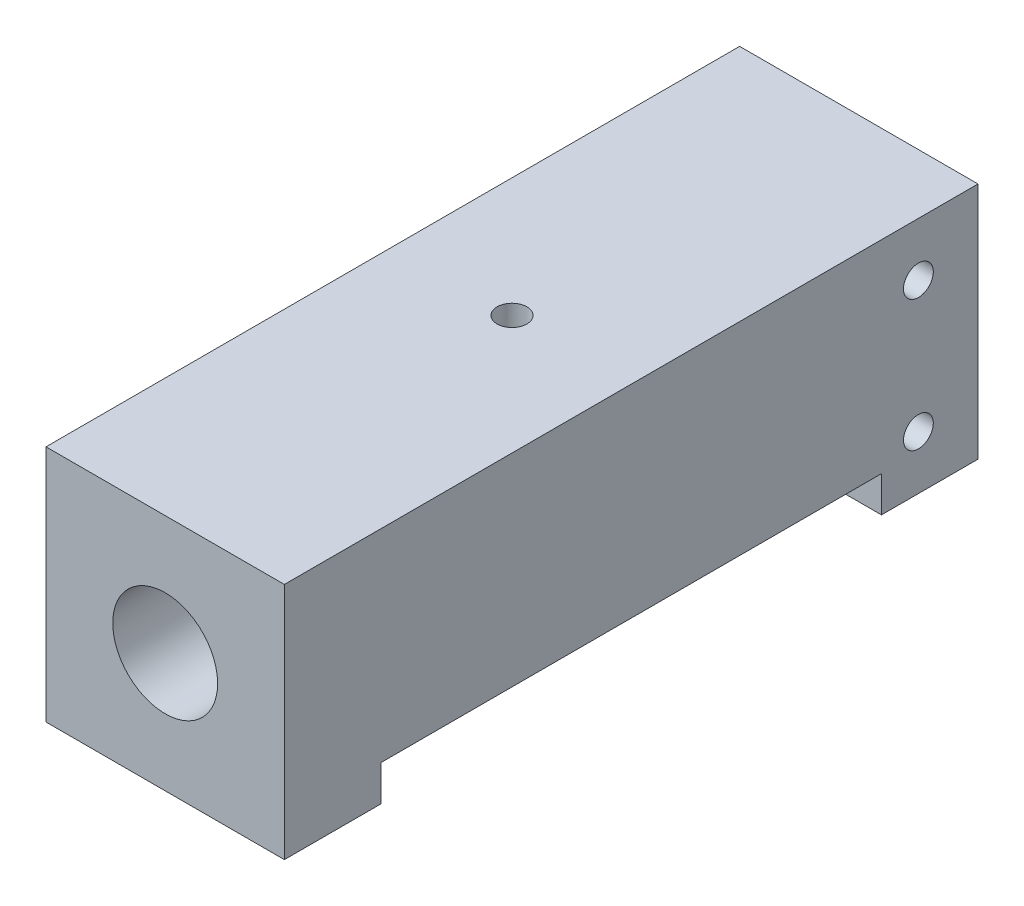
SolidWorks part; units mm, degrees
material "6063-T5"
ref_plane "Piano frontale" through (0, 0, 0) normal (0, 0, 1) x (1, 0, 0)
ref_plane "Piano superiore" through (0, 0, 0) normal (0, 1, 0) x (1, 0, 0)
ref_plane "Piano destro" through (0, 0, 0) normal (1, 0, 0) x (0, 0, -1)
sketch "Schizzo1" plane through (0, 0, 0) normal (0, 0, 1) x (1, 0, 0)
  line L1 (10, -10) -> (-10, -10)
  line L2 (10, -10) -> (10, 10)
  line L3 (10, 10) -> (-10, 10)
  line L4 (-10, -10) -> (-10, 10)
  line L5 (10, -10) -> (-10, 10) construction
  line L6 (10, 10) -> (-10, -10) construction
  point P0 (0, 0)
  dimension "D1" = 20
  dimension "D2" = 20
extrude "Estrusione-Estrusione1" add sketch "Schizzo1" against normal blind 58.2
sketch "Schizzo2" plane through (0, 0, -58.2) normal (0, 0, -1) x (-1, 0, 0)
  circle A0 centre (0, 0) radius 3
  dimension "D1" = 6
extrude "Taglio-Estrusione1" cut sketch "Schizzo2" against normal through all
sketch "Schizzo3" plane through (0, 0, -58.2) normal (0, 0, -1) x (-1, 0, 0)
  point P0 (0, 0)
hole_wizard "Foro filettato G1/8-1" positions "Schizzo8" profile "Schizzo7" tap size "G1/8" standard "BSI"
sketch "Schizzo8" plane through (0, 0, 0) normal (0, 0, 1) x (1, 0, 0)
  point P0 (0, 0)
sketch "Schizzo7" plane through (0, 0, 0) normal (1, 0, 0) x (0, -1, 0)
  line L0 (0, 0) -> (0, 12.6438)
  line L1 (0, 12.6438) -> (4.4, 10)
  line L2 (4.4, 10) -> (4.4, 0)
  line L5 (4.4, 0) -> (0, 0)
  line L10 (0, 12.6438) -> (-4.4, 10) construction
  line L11 (0, -6.35) -> (0, 107.95) construction
  dimension "Tap Drill Dia." = 8.8
  dimension "Tap Drill Depth" = 10
  dimension "Drill Angle" = 118
sketch "Schizzo11" plane through (0, 10, 0) normal (0, 1, 0) x (1, 0, 0)
  line L0 (0, 58.2) -> (0, 0) construction
  line L1 (10, 58.2) -> (-10, 58.2) construction
  line L2 (10, 29.1) -> (-10, 29.1) construction
  line L3 (10, 58.2) -> (10, 0) construction
  point P10 (0, 29.1)
  point P11 (0, 29.1)
  point P12 (0, 29.1)
hole_wizard "M3 Tapped Hole2" positions "Schizzo3D1" profile "Schizzo12" tap size "M3" standard "DIN"
sketch3d "Schizzo3D1"
  point P0 (0, 10, -29.1)
sketch "Schizzo12" plane through (0, 10, -29.1) normal (1, 0, 0) x (0, 0, 1)
  line L0 (0, 0) -> (0, 5.7511)
  line L1 (0, 5.7511) -> (1.25, 5)
  line L2 (1.25, 5) -> (1.25, 0)
  line L5 (1.25, 0) -> (0, 0)
  line L10 (0, 5.7511) -> (-1.25, 5) construction
  line L11 (0, -6.35) -> (0, 107.95) construction
  dimension "Tap Drill Dia." = 2.5
  dimension "Tap Drill Depth" = 5
  dimension "Drill Angle" = 118
cosmetic thread "Hole Thread4" parameters "D1"=5, "D2"=3
hole_wizard "Foro Ø16.0 (16)-1" positions "Schizzo3D3" profile "Schizzo14" hole size "Ø16.0" standard "ISO"
sketch3d "Schizzo3D3"
  point P0 (0, 0, 0)
  point P3 (0, 0, -58.2)
sketch "Schizzo14" plane through (0, 0, -58.2) normal (1, 0, 0) x (0, 1, 0)
  line L0 (0, 0) -> (0, 16.8069)
  line L1 (0, 16.8069) -> (8, 12)
  line L2 (8, 12) -> (8, 0)
  line L5 (8, 0) -> (0, 0)
  line L10 (0, 16.8069) -> (-8, 12) construction
  line L11 (0, -6.35) -> (0, 107.95) construction
  dimension "Hole Dia." = 16
  dimension "Hole Depth" = 12
  dimension "Drill Angle" = 118
sketch "Schizzo15" plane through (10, 0, 0) normal (1, 0, 0) x (0, 0, -1)
  line L0 (46.2, 0) -> (58.2, 0) construction
  line L1 (46.2, 8) -> (46.2, -8) construction
  line L4 (58.2, -10) -> (58.2, 10) construction
  line L6 (58.2, -10) -> (0, -10) construction
  point P5 (53.2, -5.5)
  point P8 (53.2, 5.5)
  dimension "D1" = 5.5
  dimension "D2" = 7
  dimension "D3" = 5
  dimension "D4" = 4.5
hole_wizard "M3 Tapped Hole3" positions "Schizzo3D4" profile "Schizzo16" tap size "M3" standard "ISO" end condition through all
sketch3d "Schizzo3D4"
  point P0 (10, 5.5, -53.2)
  point P3 (10, -5.5, -53.2)
sketch "Schizzo16" plane through (10, 5.5, -53.2) normal (0, 1, 0) x (0, 0, -1)
  line L0 (0, 0) -> (0, 20)
  line L1 (0, 20) -> (1.25, 20)
  line L2 (1.25, 20) -> (1.25, 0)
  line L5 (1.25, 0) -> (0, 0)
  line L11 (0, -6.35) -> (0, 107.95) construction
  dimension "Thread Major Dia." = 2.5
  dimension "Thru Tap Drill Depth" = 20
sketch "Sketch1" plane through (-10, 0, 0) normal (-1, 0, 0) x (0, 0, 1)
  line L0 (-58.2, 10) -> (-58.2, -10) construction
  line L1 (-58.2, 3) -> (-22, 3)
  line L2 (-58.2, 3) -> (-58.2, -3)
  line L3 (-58.2, -3) -> (-22, -3)
  line L4 (-22, 3) -> (-22, -3)
  line L5 (0, 10) -> (0, -10) construction
  line L6 (0, 0) -> (-22, 0) construction
  point P8 (-22, 0)
  dimension "D1" = 6
  dimension "D2" = 22
extrude "Boss-Extrude1" add sketch "Sketch1" along normal blind 4.9
sketch "Sketch2" plane through (10, 0, 0) normal (1, 0, 0) x (0, 0, -1)
  line L0 (58.2, -10) -> (0, -10) construction
  line L1 (50.1, -10) -> (34.1, -10)
  line L2 (50.1, -10) -> (50.1, -7)
  line L3 (50.1, -7) -> (34.1, -7)
  line L4 (34.1, -7) -> (8.1, -7)
  line L5 (42.1, -7) -> (42.1, -12.5) construction
  line L6 (8.1, -7) -> (8.1, -10)
  line L7 (8.1, -10) -> (34.1, -10)
  line L8 (0, -10) -> (8.1, -10) construction
  line L9 (50.1, -10) -> (58.2, -10) construction
  circle A2 centre (42.1, -12.5) radius 4 construction
  dimension "D1" = 16
  dimension "D2" = 3
extrude "Cut-Extrude1" cut sketch "Sketch2" against normal through all
sketch "Sketch3" plane through (0, 0, -22) normal (0, 0, 1) x (1, 0, 0)
  point P0 (-13, 0)
hole_wizard "M3 Tapped Hole4" positions "Sketch6" profile "Sketch7" tap size "M3" standard "ISO"
sketch "Sketch6" plane through (0, 0, -22) normal (0, 0, 1) x (1, 0, 0)
  point P0 (-13, 0)
sketch "Sketch7" plane through (-13, 0, -22) normal (1, 0, 0) x (0, -1, 0)
  line L0 (0, 0) -> (0, 20.7511)
  line L1 (0, 20.7511) -> (1.25, 20)
  line L2 (1.25, 20) -> (1.25, 0)
  line L5 (1.25, 0) -> (0, 0)
  line L10 (0, 20.7511) -> (-1.25, 20) construction
  line L11 (0, -6.35) -> (0, 107.95) construction
  dimension "Tap Drill Dia." = 2.5
  dimension "Tap Drill Depth" = 20
  dimension "Drill Angle" = 118
